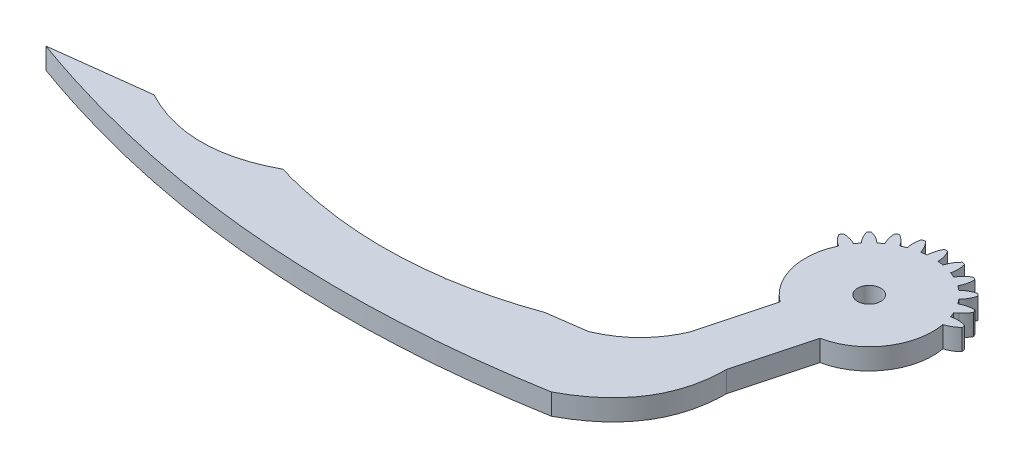
SolidWorks part; units mm, degrees
note: The reader was unsure of these and kept them because the rebuilt part matched: shared geometry of "Sketch6<3>".
ref_plane "Front Plane" through (0, 0, 0) normal (0, 0, 1) x (1, 0, 0)
ref_plane "Top Plane" through (0, 0, 0) normal (0, 1, 0) x (1, 0, 0)
ref_plane "Right Plane" through (0, 0, 0) normal (1, 0, 0) x (0, 0, -1)
sketch "Sketch1" plane through (0, 0, 0) normal (0, 1, 0) x (1, 0, 0)
  line L0 (19.8585, 7.9795) -> (1.4553, 5.5566)
  line L1 (2.4995, -2.3749) -> (20.9027, 0.0479)
  arc A0 (1.4553, 5.5566) -> (2.7124, 7.0406) centre (-1.969, 9.7321) ccw
  arc A1 (2.7124, 7.0406) -> (2.4004, 7.5811) centre (-10.1063, 0) ccw
  arc A2 (2.4004, 7.5811) -> (-0.1918, 6.9236) centre (2.3906, 2.1811) ccw
  arc A3 (-0.1918, 6.9236) -> (-0.8526, 7.7848) centre (-10.1063, 0) ccw
  arc A4 (-0.8526, 7.7848) -> (0.4534, 10.1184) centre (-4.7651, 11.5066) ccw
  arc A5 (0.4534, 10.1184) -> (0.0121, 10.5598) centre (-10.1063, 0) ccw
  arc A6 (0.0121, 10.5598) -> (-2.3216, 9.2538) centre (1.4003, 5.3412) ccw
  arc A7 (-2.3216, 9.2538) -> (-3.1827, 9.9145) centre (-10.1063, 0) ccw
  arc A8 (-3.1827, 9.9145) -> (-2.5252, 12.5067) centre (-7.9252, 12.4969) ccw
  arc A9 (-2.5252, 12.5067) -> (-3.0658, 12.8188) centre (-10.1063, 0) ccw
  arc A10 (-3.0658, 12.8188) -> (-4.9819, 10.9533) centre (-0.3742, 8.1374) ccw
  arc A11 (-4.9819, 10.9533) -> (-5.9847, 11.3687) centre (-10.1063, 0) ccw
  arc A12 (-5.9847, 11.3687) -> (-6.0205, 14.0427) centre (-11.234, 12.6356) ccw
  arc A13 (-6.0205, 14.0427) -> (-6.6234, 14.2042) centre (-10.1063, 0) ccw
  arc A14 (-6.6234, 14.2042) -> (-7.9914, 11.9064) centre (-2.812, 10.379) ccw
  arc A15 (-7.9914, 11.9064) -> (-9.0676, 12.0481) centre (-10.1063, 0) ccw
  arc A16 (-9.0676, 12.0481) -> (-9.7943, 14.6217) centre (-14.4659, 11.9132) ccw
  arc A17 (-9.7943, 14.6217) -> (-10.4184, 14.6217) centre (-10.1063, 0) ccw
  arc A18 (-10.4184, 14.6217) -> (-11.1451, 12.0481) centre (-5.7468, 11.9132) ccw
  arc A19 (-11.1451, 12.0481) -> (-12.2213, 11.9064) centre (-10.1063, 0) ccw
  arc A20 (-12.2213, 11.9064) -> (-13.5893, 14.2042) centre (-17.4007, 10.379) ccw
  arc A21 (-13.5893, 14.2042) -> (-14.1922, 14.0427) centre (-10.1063, 0) ccw
  arc A22 (-14.1922, 14.0427) -> (-14.228, 11.3687) centre (-8.9787, 12.6356) ccw
  arc A23 (-14.228, 11.3687) -> (-15.2308, 10.9533) centre (-10.1063, 0) ccw
  arc A24 (-15.2308, 10.9533) -> (-17.1469, 12.8188) centre (-19.8385, 8.1374) ccw
  arc A25 (-17.1469, 12.8188) -> (-17.6875, 12.5067) centre (-10.1063, 0) ccw
  arc A26 (-17.6875, 12.5067) -> (-17.03, 9.9145) centre (-12.2875, 12.4969) ccw
  arc A27 (-17.03, 9.9145) -> (-17.8911, 9.2538) centre (-10.1063, 0) ccw
  arc A28 (-17.8911, 9.2538) -> (-20.2247, 10.5598) centre (-21.6129, 5.3412) ccw
  arc A29 (-20.2247, 10.5598) -> (-20.6661, 10.1184) centre (-10.1063, 0) ccw
  arc A30 (-20.6661, 10.1184) -> (-19.3601, 7.7848) centre (-15.4476, 11.5066) ccw
  arc A31 (-19.3601, 7.7848) -> (-20.0209, 6.9236) centre (-10.1063, 0) ccw
  arc A32 (-20.0209, 6.9236) -> (-22.613, 7.5811) centre (-22.6033, 2.1811) ccw
  arc A33 (-22.613, 7.5811) -> (-22.9251, 7.0406) centre (-10.1063, 0) ccw
  arc A34 (-22.9251, 7.0406) -> (-21.0596, 5.1244) centre (-18.2437, 9.7321) ccw
  arc A35 (-21.0596, 5.1244) -> (-21.475, 4.1216) centre (-10.1063, 0) ccw
  arc A36 (-21.475, 4.1216) -> (-24.149, 4.0858) centre (-22.742, -1.1276) ccw
  arc A37 (-24.149, 4.0858) -> (-24.3106, 3.4829) centre (-10.1063, 0) ccw
  arc A38 (-24.3106, 3.4829) -> (-22.0127, 2.1149) centre (-20.4853, 7.2944) ccw
  arc A39 (-22.0127, 2.1149) -> (-22.1544, 1.0388) centre (-10.1063, 0) ccw
  arc A40 (-22.1544, 1.0388) -> (-24.728, 0.3121) centre (-22.0196, -4.3596) ccw
  arc A41 (-24.728, 0.3121) -> (-24.728, -0.3121) centre (-10.1063, 0) ccw
  arc A42 (-24.728, -0.3121) -> (-22.1544, -1.0388) centre (-22.0196, 4.3596) ccw
  arc A43 (-22.1544, -1.0388) -> (-22.0127, -2.1149) centre (-10.1063, 0) ccw
  arc A44 (-22.0127, -2.1149) -> (-24.3106, -3.4829) centre (-20.4853, -7.2944) ccw
  arc A45 (-24.3106, -3.4829) -> (-24.149, -4.0858) centre (-10.1063, 0) ccw
  arc A46 (-24.149, -4.0858) -> (-21.475, -4.1216) centre (-22.742, 1.1276) ccw
  arc A47 (-21.475, -4.1216) -> (-21.0596, -5.1244) centre (-10.1063, 0) ccw
  arc A48 (-21.0596, -5.1244) -> (-22.9251, -7.0406) centre (-18.2437, -9.7321) ccw
  arc A49 (-22.9251, -7.0406) -> (-22.613, -7.5811) centre (-10.1063, 0) ccw
  arc A50 (-22.613, -7.5811) -> (-20.0209, -6.9236) centre (-22.6033, -2.1811) ccw
  arc A51 (-20.0209, -6.9236) -> (-19.3601, -7.7848) centre (-10.1063, 0) ccw
  arc A52 (-19.3601, -7.7848) -> (-20.6661, -10.1184) centre (-15.4476, -11.5066) ccw
  arc A53 (-20.6661, -10.1184) -> (-20.2247, -10.5598) centre (-10.1063, 0) ccw
  arc A54 (-20.2247, -10.5598) -> (-17.8911, -9.2538) centre (-21.6129, -5.3412) ccw
  arc A55 (-17.8911, -9.2538) -> (-17.03, -9.9145) centre (-10.1063, 0) ccw
  arc A56 (-17.03, -9.9145) -> (-17.6875, -12.5067) centre (-12.2875, -12.4969) ccw
  arc A57 (-17.6875, -12.5067) -> (-17.1469, -12.8188) centre (-10.1063, 0) ccw
  arc A58 (-17.1469, -12.8188) -> (-15.2308, -10.9533) centre (-19.8385, -8.1374) ccw
  arc A59 (-15.2308, -10.9533) -> (-14.228, -11.3687) centre (-10.1063, 0) ccw
  arc A60 (-14.228, -11.3687) -> (-14.1922, -14.0427) centre (-8.9787, -12.6356) ccw
  arc A61 (-14.1922, -14.0427) -> (-13.5893, -14.2042) centre (-10.1063, 0) ccw
  arc A62 (-13.5893, -14.2042) -> (-12.2213, -11.9064) centre (-17.4007, -10.379) ccw
  arc A63 (-12.2213, -11.9064) -> (-11.1451, -12.0481) centre (-10.1063, 0) ccw
  arc A64 (-11.1451, -12.0481) -> (-10.4184, -14.6217) centre (-5.7468, -11.9132) ccw
  arc A65 (-10.4184, -14.6217) -> (-9.7943, -14.6217) centre (-10.1063, 0) ccw
  arc A66 (-9.7943, -14.6217) -> (-9.0676, -12.0481) centre (-14.4659, -11.9132) ccw
  arc A67 (-9.0676, -12.0481) -> (-7.9914, -11.9064) centre (-10.1063, 0) ccw
  arc A68 (-7.9914, -11.9064) -> (-6.6234, -14.2042) centre (-2.812, -10.379) ccw
  arc A69 (-6.6234, -14.2042) -> (-6.0205, -14.0427) centre (-10.1063, 0) ccw
  arc A70 (-6.0205, -14.0427) -> (-5.9847, -11.3687) centre (-11.234, -12.6356) ccw
  arc A71 (-5.9847, -11.3687) -> (-4.9819, -10.9533) centre (-10.1063, 0) ccw
  arc A72 (-4.9819, -10.9533) -> (-3.0658, -12.8188) centre (-0.3742, -8.1374) ccw
  arc A73 (-3.0658, -12.8188) -> (-2.5252, -12.5067) centre (-10.1063, 0) ccw
  arc A74 (-2.5252, -12.5067) -> (-3.1827, -9.9145) centre (-7.9252, -12.4969) ccw
  arc A75 (-3.1827, -9.9145) -> (-2.3216, -9.2538) centre (-10.1063, 0) ccw
  arc A76 (-2.3216, -9.2538) -> (0.0121, -10.5598) centre (1.4003, -5.3412) ccw
  arc A77 (0.0121, -10.5598) -> (0.4534, -10.1184) centre (-10.1063, 0) ccw
  arc A78 (0.4534, -10.1184) -> (-0.8526, -7.7848) centre (-4.7651, -11.5066) ccw
  arc A79 (-0.8526, -7.7848) -> (-0.1918, -6.9236) centre (-10.1063, 0) ccw
  arc A80 (-0.1918, -6.9236) -> (2.4004, -7.5811) centre (2.3906, -2.1811) ccw
  arc A81 (2.4004, -7.5811) -> (2.7124, -7.0406) centre (-10.1063, 0) ccw
  arc A82 (2.7124, -7.0406) -> (0.847, -5.1244) centre (-1.969, -9.7321) ccw
  arc A83 (0.847, -5.1244) -> (1.2623, -4.1216) centre (-10.1063, 0) ccw
  arc A84 (1.2623, -4.1216) -> (3.9363, -4.0858) centre (2.5293, 1.1276) ccw
  arc A85 (3.9363, -4.0858) -> (4.0979, -3.4829) centre (-10.1063, 0) ccw
  arc A86 (4.0979, -3.4829) -> (2.4995, -2.3749) centre (0.2726, -7.2944) ccw
  arc A87 (20.9027, 0.0479) -> (19.8585, 7.9795) centre (20.3806, 4.0137) ccw
  circle A88 centre (-10.1063, 0) radius 1.5
  circle A89 centre (20.3806, 4.0137) radius 1.5
  dimension "D1" = 3
  dimension "D2" = 3
extrude "Boss-Extrude1" add sketch "Sketch1" along normal blind 4
sketch "Sketch3" plane through (0, 4, 0) normal (0, 1, 0) x (1, 0, 0)
  line L0 (-10.1063, 0) -> (-40.8563, 0) construction
  line L1 (-10.1063, 0) -> (-40.5933, -4.0137)
  line L2 (-10.6284, 3.9658) -> (-41.1154, -0.0479)
  line L3 (-9.5842, -3.9658) -> (-40.0712, -7.9795)
  line L4 (-10.1063, 0) -> (-6.3211, 14.1267) construction
  line L5 (-10.1063, 0) -> (-10.1063, 14.625) construction
  circle A0 centre (-10.1063, 0) radius 1.5
  circle A1 centre (20.3806, 4.0137) radius 1.5 construction
  circle A2 centre (20.3806, 4.0137) radius 1.5
  circle A3 centre (-40.5933, -4.0137) radius 1.75
  circle A4 centre (-40.5933, -4.0137) radius 4
  circle A5 centre (-10.1063, 0) radius 4
  arc A6 (-6.0205, 14.0427) -> (-6.6234, 14.2042) centre (-10.1063, 0) ccw construction
  arc A7 (-9.7943, 14.6217) -> (-10.4184, 14.6217) centre (-10.1063, 0) ccw construction
  dimension "D2" = 3
  dimension "D5" = 3.5
  dimension "D6" = 8
  dimension "D7" = 8
  dimension "D1" = 30.75
  dimension "D4" = 7.5
extrude "Boss-Extrude2" add sketch "Sketch3" against normal blind 4
sketch "Sketch4" plane through (0, 4, 0) normal (0, 1, 0) x (1, 0, 0)
  line L0 (19.8585, 7.9795) -> (1.4553, 5.5566) construction
  line L1 (2.4995, -2.3749) -> (20.9027, 0.0479) construction
  line L2 (19.8585, 7.9795) -> (1.4553, 5.5566)
  line L3 (2.4995, -2.3749) -> (20.9027, 0.0479)
  line L4 (1.4553, 5.5566) -> (0.8694, 5.0762)
  line L5 (-21.6245, -5.5509) -> (-20.8986, -5.4553)
  line L6 (-10.1063, 0) -> (-0.8526, 7.7848) construction
  line L7 (-10.1063, 0) -> (1.8, 2.1149) construction
  line L8 (-22.7122, 2.3749) -> (-41.1154, -0.0479)
  line L9 (-40.0712, -7.9795) -> (-21.668, -5.5566)
  line L10 (2.4995, -2.3749) -> (20.9027, 0.0479)
  line L11 (19.8585, 7.9795) -> (1.4553, 5.5566)
  line L12 (-21.9429, 2.4762) -> (-41.1154, -0.0479)
  line L13 (-40.0712, -7.9795) -> (-21.6245, -5.5509)
  line L14 (2.4995, -2.3749) -> (20.9027, 0.0479)
  line L15 (19.8585, 7.9795) -> (1.4553, 5.5566)
  circle A0 centre (-10.1063, 0) radius 12.0927
  arc A1 (2.4004, 7.5811) -> (-0.1918, 6.9236) centre (2.3906, 2.1811) ccw construction
  arc A2 (2.7124, 7.0406) -> (2.4004, 7.5811) centre (-10.1063, 0) ccw construction
  arc A3 (1.4553, 5.5566) -> (2.7124, 7.0406) centre (-1.969, 9.7321) ccw construction
  arc A4 (20.9027, 0.0479) -> (19.8585, 7.9795) centre (20.3806, 4.0137) ccw construction
  arc A5 (4.0979, -3.4829) -> (2.4995, -2.3749) centre (0.2726, -7.2944) ccw construction
  arc A6 (3.9363, -4.0858) -> (4.0979, -3.4829) centre (-10.1063, 0) ccw construction
  arc A7 (1.2623, -4.1216) -> (3.9363, -4.0858) centre (2.5293, 1.1276) ccw construction
  arc A8 (2.4004, 7.5811) -> (-0.1918, 6.9236) centre (2.3906, 2.1811) ccw
  arc A9 (2.7124, 7.0406) -> (2.4004, 7.5811) centre (-10.1063, 0) ccw
  arc A10 (1.4553, 5.5566) -> (2.7124, 7.0406) centre (-1.969, 9.7321) ccw
  arc A11 (20.9027, 0.0479) -> (19.8585, 7.9795) centre (20.3806, 4.0137) ccw
  arc A12 (4.0979, -3.4829) -> (2.4995, -2.3749) centre (0.2726, -7.2944) ccw
  arc A13 (3.9363, -4.0858) -> (4.0979, -3.4829) centre (-10.1063, 0) ccw
  arc A14 (1.2623, -4.1216) -> (3.9363, -4.0858) centre (2.5293, 1.1276) ccw
  arc A15 (1.8, 2.1149) -> (4.0979, 3.4829) centre (0.2726, 7.2944) ccw
  arc A16 (3.9363, 4.0858) -> (1.2623, 4.1216) centre (2.5293, -1.1276) ccw
  arc A17 (4.0979, 3.4829) -> (3.9363, 4.0858) centre (-10.1063, 0) ccw
  arc A95 (-21.668, -5.5566) -> (-22.9251, -7.0406) centre (-18.2437, -9.7321) ccw
  arc A96 (-41.1154, -0.0479) -> (-40.0712, -7.9795) centre (-40.5933, -4.0137) ccw
  arc A97 (-19.3601, -7.7848) -> (-20.6661, -10.1184) centre (-15.4476, -11.5066) ccw
  arc A98 (-20.6661, -10.1184) -> (-20.2247, -10.5598) centre (-10.1063, 0) ccw
  arc A99 (-20.2247, -10.5598) -> (-17.8911, -9.2538) centre (-21.6129, -5.3412) ccw
  arc A100 (-17.8911, -9.2538) -> (-17.03, -9.9145) centre (-10.1063, 0) ccw
  arc A101 (-17.03, -9.9145) -> (-17.6875, -12.5067) centre (-12.2875, -12.4969) ccw
  arc A102 (-17.6875, -12.5067) -> (-17.1469, -12.8188) centre (-10.1063, 0) ccw
  arc A103 (-17.1469, -12.8188) -> (-15.2308, -10.9533) centre (-19.8385, -8.1374) ccw
  arc A104 (-15.2308, -10.9533) -> (-14.228, -11.3687) centre (-10.1063, 0) ccw
  arc A105 (-14.228, -11.3687) -> (-14.1922, -14.0427) centre (-8.9787, -12.6356) ccw
  arc A106 (-14.1922, -14.0427) -> (-13.5893, -14.2042) centre (-10.1063, 0) ccw
  arc A107 (-13.5893, -14.2042) -> (-12.2213, -11.9064) centre (-17.4007, -10.379) ccw
  arc A108 (-12.2213, -11.9064) -> (-11.1451, -12.0481) centre (-10.1063, 0) ccw
  arc A109 (-11.1451, -12.0481) -> (-10.4184, -14.6217) centre (-5.7468, -11.9132) ccw
  arc A110 (-10.4184, -14.6217) -> (-9.7943, -14.6217) centre (-10.1063, 0) ccw
  arc A111 (-9.7943, -14.6217) -> (-9.0676, -12.0481) centre (-14.4659, -11.9132) ccw
  arc A112 (-9.0676, -12.0481) -> (-7.9914, -11.9064) centre (-10.1063, 0) ccw
  arc A113 (-7.9914, -11.9064) -> (-6.6234, -14.2042) centre (-2.812, -10.379) ccw
  arc A114 (-6.6234, -14.2042) -> (-6.0205, -14.0427) centre (-10.1063, 0) ccw
  arc A115 (-6.0205, -14.0427) -> (-5.9847, -11.3687) centre (-11.234, -12.6356) ccw
  arc A116 (-5.9847, -11.3687) -> (-4.9819, -10.9533) centre (-10.1063, 0) ccw
  arc A117 (-4.9819, -10.9533) -> (-3.0658, -12.8188) centre (-0.3742, -8.1374) ccw
  arc A118 (-3.0658, -12.8188) -> (-2.5252, -12.5067) centre (-10.1063, 0) ccw
  arc A119 (-2.5252, -12.5067) -> (-3.1827, -9.9145) centre (-7.9252, -12.4969) ccw
  arc A120 (-3.1827, -9.9145) -> (-2.3216, -9.2538) centre (-10.1063, 0) ccw
  arc A121 (-2.3216, -9.2538) -> (0.0121, -10.5598) centre (1.4003, -5.3412) ccw
  arc A122 (0.0121, -10.5598) -> (0.4534, -10.1184) centre (-10.1063, 0) ccw
  arc A123 (0.4534, -10.1184) -> (-0.8526, -7.7848) centre (-4.7651, -11.5066) ccw
  arc A124 (-0.8526, -7.7848) -> (-0.1918, -6.9236) centre (-10.1063, 0) ccw
  arc A125 (-0.1918, -6.9236) -> (2.4004, -7.5811) centre (2.3906, -2.1811) ccw
  arc A126 (2.4004, -7.5811) -> (2.7124, -7.0406) centre (-10.1063, 0) ccw
  arc A127 (2.7124, -7.0406) -> (0.847, -5.1244) centre (-1.969, -9.7321) ccw
  arc A128 (0.847, -5.1244) -> (1.2623, -4.1216) centre (-10.1063, 0) ccw
  arc A129 (1.2623, -4.1216) -> (3.9363, -4.0858) centre (2.5293, 1.1276) ccw
  arc A130 (3.9363, -4.0858) -> (4.0979, -3.4829) centre (-10.1063, 0) ccw
  arc A131 (4.0979, -3.4829) -> (2.4995, -2.3749) centre (0.2726, -7.2944) ccw
  arc A132 (20.9027, 0.0479) -> (19.8585, 7.9795) centre (20.3806, 4.0137) ccw
  arc A133 (1.4553, 5.5566) -> (2.7124, 7.0406) centre (-1.969, 9.7321) ccw
  arc A134 (2.7124, 7.0406) -> (2.4004, 7.5811) centre (-10.1063, 0) ccw
  arc A135 (2.4004, 7.5811) -> (-0.1918, 6.9236) centre (2.3906, 2.1811) ccw
  arc A136 (-0.1918, 6.9236) -> (-0.8526, 7.7848) centre (-10.1063, 0) ccw
  arc A137 (-0.8526, 7.7848) -> (0.4534, 10.1184) centre (-4.7651, 11.5066) ccw
  arc A138 (0.4534, 10.1184) -> (0.0121, 10.5598) centre (-10.1063, 0) ccw
  arc A139 (0.0121, 10.5598) -> (-2.3216, 9.2538) centre (1.4003, 5.3412) ccw
  arc A140 (-2.3216, 9.2538) -> (-3.1827, 9.9145) centre (-10.1063, 0) ccw
  arc A141 (-3.1827, 9.9145) -> (-2.5252, 12.5067) centre (-7.9252, 12.4969) ccw
  arc A142 (-2.5252, 12.5067) -> (-3.0658, 12.8188) centre (-10.1063, 0) ccw
  arc A143 (-3.0658, 12.8188) -> (-4.9819, 10.9533) centre (-0.3742, 8.1374) ccw
  arc A144 (-4.9819, 10.9533) -> (-5.9847, 11.3687) centre (-10.1063, 0) ccw
  arc A145 (-5.9847, 11.3687) -> (-6.0205, 14.0427) centre (-11.234, 12.6356) ccw
  arc A146 (-6.0205, 14.0427) -> (-6.6234, 14.2042) centre (-10.1063, 0) ccw
  arc A147 (-6.6234, 14.2042) -> (-7.9914, 11.9064) centre (-2.812, 10.379) ccw
  arc A148 (-7.9914, 11.9064) -> (-9.0676, 12.0481) centre (-10.1063, 0) ccw
  arc A149 (-9.0676, 12.0481) -> (-9.7943, 14.6217) centre (-14.4659, 11.9132) ccw
  arc A150 (-9.7943, 14.6217) -> (-10.4184, 14.6217) centre (-10.1063, 0) ccw
  arc A151 (-10.4184, 14.6217) -> (-11.1451, 12.0481) centre (-5.7468, 11.9132) ccw
  arc A152 (-11.1451, 12.0481) -> (-12.2213, 11.9064) centre (-10.1063, 0) ccw
  arc A153 (-12.2213, 11.9064) -> (-13.5893, 14.2042) centre (-17.4007, 10.379) ccw
  arc A154 (-13.5893, 14.2042) -> (-14.1922, 14.0427) centre (-10.1063, 0) ccw
  arc A155 (-14.1922, 14.0427) -> (-14.228, 11.3687) centre (-8.9787, 12.6356) ccw
  arc A156 (-14.228, 11.3687) -> (-15.2308, 10.9533) centre (-10.1063, 0) ccw
  arc A157 (-15.2308, 10.9533) -> (-17.1469, 12.8188) centre (-19.8385, 8.1374) ccw
  arc A158 (-17.1469, 12.8188) -> (-17.6875, 12.5067) centre (-10.1063, 0) ccw
  arc A159 (-17.6875, 12.5067) -> (-17.03, 9.9145) centre (-12.2875, 12.4969) ccw
  arc A160 (-17.03, 9.9145) -> (-17.8911, 9.2538) centre (-10.1063, 0) ccw
  arc A161 (-17.8911, 9.2538) -> (-20.2247, 10.5598) centre (-21.6129, 5.3412) ccw
  arc A162 (-20.2247, 10.5598) -> (-20.6661, 10.1184) centre (-10.1063, 0) ccw
  arc A163 (-20.6661, 10.1184) -> (-19.3601, 7.7848) centre (-15.4476, 11.5066) ccw
  arc A164 (-19.3601, 7.7848) -> (-20.0209, 6.9236) centre (-10.1063, 0) ccw
  arc A165 (-20.0209, 6.9236) -> (-22.613, 7.5811) centre (-22.6033, 2.1811) ccw
  arc A166 (-22.613, 7.5811) -> (-22.9251, 7.0406) centre (-10.1063, 0) ccw
  arc A167 (-22.9251, 7.0406) -> (-21.0596, 5.1244) centre (-18.2437, 9.7321) ccw
  arc A168 (-21.0596, 5.1244) -> (-21.475, 4.1216) centre (-10.1063, 0) ccw
  arc A169 (-21.475, 4.1216) -> (-24.149, 4.0858) centre (-22.742, -1.1276) ccw
  arc A170 (-24.149, 4.0858) -> (-24.3106, 3.4829) centre (-10.1063, 0) ccw
  arc A171 (-24.3106, 3.4829) -> (-22.7122, 2.3749) centre (-20.4853, 7.2944) ccw
  arc A172 (-21.668, -5.5566) -> (-22.9251, -7.0406) centre (-18.2437, -9.7321) ccw
  arc A175 (-22.613, -7.5811) -> (-20.0209, -6.9236) centre (-22.6033, -2.1811) ccw
  arc A176 (-41.1154, -0.0479) -> (-40.0712, -7.9795) centre (-40.5933, -4.0137) ccw
  arc A177 (-19.3601, -7.7848) -> (-20.6661, -10.1184) centre (-15.4476, -11.5066) ccw
  arc A178 (-20.6661, -10.1184) -> (-20.2247, -10.5598) centre (-10.1063, 0) ccw
  arc A179 (-20.2247, -10.5598) -> (-17.8911, -9.2538) centre (-21.6129, -5.3412) ccw
  arc A180 (-17.8911, -9.2538) -> (-17.03, -9.9145) centre (-10.1063, 0) ccw
  arc A181 (-17.03, -9.9145) -> (-17.6875, -12.5067) centre (-12.2875, -12.4969) ccw
  arc A182 (-17.6875, -12.5067) -> (-17.1469, -12.8188) centre (-10.1063, 0) ccw
  arc A183 (-17.1469, -12.8188) -> (-15.2308, -10.9533) centre (-19.8385, -8.1374) ccw
  arc A184 (-15.2308, -10.9533) -> (-14.228, -11.3687) centre (-10.1063, 0) ccw
  arc A185 (-14.228, -11.3687) -> (-14.1922, -14.0427) centre (-8.9787, -12.6356) ccw
  arc A186 (-14.1922, -14.0427) -> (-13.5893, -14.2042) centre (-10.1063, 0) ccw
  arc A187 (-13.5893, -14.2042) -> (-12.2213, -11.9064) centre (-17.4007, -10.379) ccw
  arc A188 (-12.2213, -11.9064) -> (-11.1451, -12.0481) centre (-10.1063, 0) ccw
  arc A189 (-11.1451, -12.0481) -> (-10.4184, -14.6217) centre (-5.7468, -11.9132) ccw
  arc A190 (-10.4184, -14.6217) -> (-9.7943, -14.6217) centre (-10.1063, 0) ccw
  arc A191 (-9.7943, -14.6217) -> (-9.0676, -12.0481) centre (-14.4659, -11.9132) ccw
  arc A192 (-9.0676, -12.0481) -> (-7.9914, -11.9064) centre (-10.1063, 0) ccw
  arc A193 (-7.9914, -11.9064) -> (-6.6234, -14.2042) centre (-2.812, -10.379) ccw
  arc A194 (-6.6234, -14.2042) -> (-6.0205, -14.0427) centre (-10.1063, 0) ccw
  arc A195 (-6.0205, -14.0427) -> (-5.9847, -11.3687) centre (-11.234, -12.6356) ccw
  arc A196 (-5.9847, -11.3687) -> (-4.9819, -10.9533) centre (-10.1063, 0) ccw
  arc A197 (-4.9819, -10.9533) -> (-3.0658, -12.8188) centre (-0.3742, -8.1374) ccw
  arc A198 (-3.0658, -12.8188) -> (-2.5252, -12.5067) centre (-10.1063, 0) ccw
  arc A199 (-2.5252, -12.5067) -> (-3.1827, -9.9145) centre (-7.9252, -12.4969) ccw
  arc A200 (-3.1827, -9.9145) -> (-2.3216, -9.2538) centre (-10.1063, 0) ccw
  arc A201 (-2.3216, -9.2538) -> (0.0121, -10.5598) centre (1.4003, -5.3412) ccw
  arc A202 (0.0121, -10.5598) -> (0.4534, -10.1184) centre (-10.1063, 0) ccw
  arc A203 (0.4534, -10.1184) -> (-0.8526, -7.7848) centre (-4.7651, -11.5066) ccw
  arc A204 (-0.8526, -7.7848) -> (-0.1918, -6.9236) centre (-10.1063, 0) ccw
  arc A205 (-0.1918, -6.9236) -> (2.4004, -7.5811) centre (2.3906, -2.1811) ccw
  arc A206 (2.4004, -7.5811) -> (2.7124, -7.0406) centre (-10.1063, 0) ccw
  arc A207 (2.7124, -7.0406) -> (0.847, -5.1244) centre (-1.969, -9.7321) ccw
  arc A208 (0.847, -5.1244) -> (1.2623, -4.1216) centre (-10.1063, 0) ccw
  arc A209 (1.2623, -4.1216) -> (3.9363, -4.0858) centre (2.5293, 1.1276) ccw
  arc A210 (3.9363, -4.0858) -> (4.0979, -3.4829) centre (-10.1063, 0) ccw
  arc A211 (4.0979, -3.4829) -> (2.4995, -2.3749) centre (0.2726, -7.2944) ccw
  arc A212 (20.9027, 0.0479) -> (19.8585, 7.9795) centre (20.3806, 4.0137) ccw
  arc A213 (1.4553, 5.5566) -> (2.7124, 7.0406) centre (-1.969, 9.7321) ccw
  arc A214 (2.7124, 7.0406) -> (2.4004, 7.5811) centre (-10.1063, 0) ccw
  arc A215 (2.4004, 7.5811) -> (-0.1918, 6.9236) centre (2.3906, 2.1811) ccw
  arc A216 (-0.1918, 6.9236) -> (-0.8526, 7.7848) centre (-10.1063, 0) ccw
  arc A217 (-0.8526, 7.7848) -> (0.4534, 10.1184) centre (-4.7651, 11.5066) ccw
  arc A218 (0.4534, 10.1184) -> (0.0121, 10.5598) centre (-10.1063, 0) ccw
  arc A219 (0.0121, 10.5598) -> (-2.3216, 9.2538) centre (1.4003, 5.3412) ccw
  arc A220 (-2.3216, 9.2538) -> (-3.1827, 9.9145) centre (-10.1063, 0) ccw
  arc A221 (-3.1827, 9.9145) -> (-2.5252, 12.5067) centre (-7.9252, 12.4969) ccw
  arc A222 (-2.5252, 12.5067) -> (-3.0658, 12.8188) centre (-10.1063, 0) ccw
  arc A223 (-3.0658, 12.8188) -> (-4.9819, 10.9533) centre (-0.3742, 8.1374) ccw
  arc A224 (-4.9819, 10.9533) -> (-5.9847, 11.3687) centre (-10.1063, 0) ccw
  arc A225 (-5.9847, 11.3687) -> (-6.0205, 14.0427) centre (-11.234, 12.6356) ccw
  arc A226 (-6.0205, 14.0427) -> (-6.6234, 14.2042) centre (-10.1063, 0) ccw
  arc A227 (-6.6234, 14.2042) -> (-7.9914, 11.9064) centre (-2.812, 10.379) ccw
  arc A228 (-7.9914, 11.9064) -> (-9.0676, 12.0481) centre (-10.1063, 0) ccw
  arc A229 (-9.0676, 12.0481) -> (-9.7943, 14.6217) centre (-14.4659, 11.9132) ccw
  arc A230 (-9.7943, 14.6217) -> (-10.4184, 14.6217) centre (-10.1063, 0) ccw
  arc A231 (-10.4184, 14.6217) -> (-11.1451, 12.0481) centre (-5.7468, 11.9132) ccw
  arc A232 (-11.1451, 12.0481) -> (-12.2213, 11.9064) centre (-10.1063, 0) ccw
  arc A233 (-12.2213, 11.9064) -> (-13.5893, 14.2042) centre (-17.4007, 10.379) ccw
  arc A234 (-13.5893, 14.2042) -> (-14.1922, 14.0427) centre (-10.1063, 0) ccw
  arc A235 (-14.1922, 14.0427) -> (-14.228, 11.3687) centre (-8.9787, 12.6356) ccw
  arc A236 (-14.228, 11.3687) -> (-15.2308, 10.9533) centre (-10.1063, 0) ccw
  arc A237 (-15.2308, 10.9533) -> (-17.1469, 12.8188) centre (-19.8385, 8.1374) ccw
  arc A238 (-17.1469, 12.8188) -> (-17.6875, 12.5067) centre (-10.1063, 0) ccw
  arc A239 (-17.6875, 12.5067) -> (-17.03, 9.9145) centre (-12.2875, 12.4969) ccw
  arc A240 (-17.03, 9.9145) -> (-17.8911, 9.2538) centre (-10.1063, 0) ccw
  arc A241 (-17.8911, 9.2538) -> (-20.2247, 10.5598) centre (-21.6129, 5.3412) ccw
  arc A242 (-20.2247, 10.5598) -> (-20.6661, 10.1184) centre (-10.1063, 0) ccw
  arc A243 (-20.6661, 10.1184) -> (-19.3601, 7.7848) centre (-15.4476, 11.5066) ccw
  arc A244 (-19.3601, 7.7848) -> (-20.0209, 6.9236) centre (-10.1063, 0) ccw
  arc A245 (-20.0209, 6.9236) -> (-22.613, 7.5811) centre (-22.6033, 2.1811) ccw
  arc A246 (-22.613, 7.5811) -> (-22.9251, 7.0406) centre (-10.1063, 0) ccw
  arc A247 (-22.9251, 7.0406) -> (-21.0596, 5.1244) centre (-18.2437, 9.7321) ccw
  arc A248 (-21.0596, 5.1244) -> (-21.475, 4.1216) centre (-10.1063, 0) ccw
  arc A249 (-21.475, 4.1216) -> (-24.149, 4.0858) centre (-22.742, -1.1276) ccw
  arc A250 (-24.149, 4.0858) -> (-24.3106, 3.4829) centre (-10.1063, 0) ccw
  arc A251 (-24.3106, 3.4829) -> (-22.7122, 2.3749) centre (-20.4853, 7.2944) ccw
  arc A252 (-22.613, -7.5811) -> (-20.0209, -6.9236) centre (-22.6033, -2.1811) ccw
  arc A253 (-20.0209, -6.9236) -> (-19.3601, -7.7848) centre (-10.1063, 0) ccw
  arc A254 (-20.0209, -6.9236) -> (-19.3601, -7.7848) centre (-10.1063, 0) ccw
  arc A255 (-22.9251, -7.0406) -> (-22.613, -7.5811) centre (-10.1063, 0) ccw
  arc A256 (-22.9251, -7.0406) -> (-22.613, -7.5811) centre (-10.1063, 0) ccw
  point P40 (-10.1063, 0)
  dimension "D2" = 24.1855
  dimension "D4" = 30
  dimension "D1" = 0
  dimension "D3" = 2
extrude "Cut-Extrude1" cut sketch "Sketch4" against normal blind 4
sketch "Sketch5" plane through (0, 4, 0) normal (0, 1, 0) x (1, 0, 0)
  circle A0 centre (-10.1063, 0) radius 2.2
  circle A1 centre (-5.6063, 0) radius 1.3
  circle A2 centre (-14.6063, 0) radius 1.3
  circle A3 centre (-10.1063, 0) radius 1.5 construction
  dimension "D1" = 4.4
  dimension "D2" = 2.6
  dimension "D3" = 2.6
  dimension "D4" = 4.5
  dimension "D5" = 9
extrude "Cut-Extrude2" cut sketch "Sketch5" against normal up to next contours A0
sketch "Sketch6" plane through (0, 4, 0) normal (0, 1, 0) x (1, 0, 0)
  line L0 (-10.1063, 0) -> (27.4558, 0) construction
  line L6 (-10.1063, 0) -> (-10.1063, 50.6275) construction
  line L7 (-49.9947, -31.0378) -> (-31.4327, -31.0378)
  line L9 (-31.4327, -31.0378) -> (-30.7345, -31.267)
  line L10 (-110.9546, -35.0378) -> (-129.2447, -37.2757)
  line L11 (-16.653, -6.8971) -> (-20.9868, -23.0712)
  line L12 (-6.9937, -9.4853) -> (-11.3793, -25.8525)
  line L15 (0.8694, 5.0762) -> (1.4553, 5.5566)
  line L16 (-7.7003, -31.4377) -> (-7.0568, -31.0378)
  line L17 (-30.7064, -32.7034) -> (-49.8584, -35.379)
  line L18 (-21.9429, 2.4762) -> (-41.1154, -0.0479)
  line L19 (-40.0712, -7.9795) -> (-20.8986, -5.4553)
  line L20 (0.8694, 5.0762) -> (1.4553, 5.5566)
  line L21 (-23.6599, -5.715) -> (-42.8324, -8.2391)
  line L22 (-41.7882, -16.1707) -> (-22.6156, -13.6466)
  line L23 (-21.9429, 2.4762) -> (-41.1154, -0.0479) construction
  line L24 (-21.9429, 2.4762) -> (-41.1154, -0.0479)
  line L25 (-20.8986, -5.4553) -> (-40.0712, -7.9795) construction
  line L26 (-20.8986, -5.4553) -> (-40.0712, -7.9795)
  arc A46 (-20.9868, -23.0712) -> (-31.1213, -32.7614) centre (-19.2447, -35.0378) ccw
  arc A92 (-4.7074, -33.4387) -> (3.539, -25.9102) centre (-0.5842, -29.6745) cw
  arc A93 (-4.7889, -32.8199) -> (-4.7074, -33.4387) centre (-19.2447, -35.0378) cw
  arc A94 (-7.4353, -32.4354) -> (-4.7889, -32.8199) centre (-6.8644, -37.8051) cw
  arc A95 (-7.7163, -31.3869) -> (-7.4353, -32.4354) centre (-19.2447, -35.0378) cw
  arc A96 (-5.6166, -29.7307) -> (-7.7163, -31.3869) centre (-9.9067, -26.4511) cw
  arc A97 (-5.8555, -29.154) -> (-5.6166, -29.7307) centre (-19.2447, -35.0378) cw
  arc A98 (-8.5113, -29.4676) -> (-5.8555, -29.154) centre (-6.57, -34.5065) cw
  arc A99 (-9.054, -28.5275) -> (-8.5113, -29.4676) centre (-19.2447, -35.0378) cw
  arc A100 (-7.4546, -26.3843) -> (-9.054, -28.5275) centre (-12.4473, -24.3268) cw
  arc A101 (-7.8346, -25.8891) -> (-7.4546, -26.3843) centre (-19.2447, -35.0378) cw
  arc A102 (-10.3187, -26.8793) -> (-7.8346, -25.8891) centre (-7.1394, -31.2442) cw
  arc A103 (-11.0863, -26.1118) -> (-10.3187, -26.8793) centre (-19.2447, -35.0378) cw
  arc A104 (-10.096, -23.6277) -> (-11.0863, -26.1118) centre (-15.4511, -22.9325) cw
  arc A105 (-10.5912, -23.2477) -> (-10.096, -23.6277) centre (-19.2447, -35.0378) cw
  arc A106 (-10.6929, -23.2908) -> (-10.5912, -23.2477) centre (-8.5337, -28.2404) cw
  arc A115 (-20.8438, -20.5005) -> (-20.4536, -21.0814) centre (-25.122, -23.7956) cw
  arc A116 (-21.4627, -20.582) -> (-20.8438, -20.5005) centre (-19.2447, -35.0378) cw
  arc A117 (-21.8472, -23.2284) -> (-21.4627, -20.582) centre (-16.4775, -22.6575) cw
  arc A118 (-22.8956, -23.5094) -> (-21.8472, -23.2284) centre (-19.2447, -35.0378) cw
  arc A119 (-24.5519, -21.4097) -> (-22.8956, -23.5094) centre (-27.8314, -25.6998) cw
  arc A120 (-25.1285, -21.6486) -> (-24.5519, -21.4097) centre (-19.2447, -35.0378) cw
  arc A121 (-24.815, -24.3044) -> (-25.1285, -21.6486) centre (-19.776, -22.3631) cw
  arc A122 (-25.755, -24.8471) -> (-24.815, -24.3044) centre (-19.2447, -35.0378) cw
  arc A123 (-27.8983, -23.2477) -> (-25.755, -24.8471) centre (-29.9557, -28.2404) cw
  arc A124 (-28.3934, -23.6277) -> (-27.8983, -23.2477) centre (-19.2447, -35.0378) cw
  arc A125 (-27.4032, -26.1118) -> (-28.3934, -23.6277) centre (-23.0384, -22.9325) cw
  arc A126 (-28.1707, -26.8793) -> (-27.4032, -26.1118) centre (-19.2447, -35.0378) cw
  arc A127 (-30.6549, -25.8891) -> (-28.1707, -26.8793) centre (-31.3501, -31.2442) cw
  arc A128 (-31.0349, -26.3843) -> (-30.6549, -25.8891) centre (-19.2447, -35.0378) cw
  arc A129 (-29.4355, -28.5275) -> (-31.0349, -26.3843) centre (-26.0422, -24.3268) cw
  arc A130 (-29.9782, -29.4676) -> (-29.4355, -28.5275) centre (-19.2447, -35.0378) cw
  arc A131 (-32.634, -29.154) -> (-29.9782, -29.4676) centre (-31.9195, -34.5065) cw
  arc A132 (-32.8728, -29.7307) -> (-32.634, -29.154) centre (-19.2447, -35.0378) cw
  arc A133 (-31.4327, -31.0378) -> (-32.8728, -29.7307) centre (-28.5828, -26.4511) cw
  arc A134 (-52.9621, -37.7202) -> (-49.9947, -31.0378) centre (-49.9947, -35.0378) cw
  arc A135 (3.539, -25.9102) -> (-24.3078, -46.1789) centre (-16.9719, -26.9941) cw
  arc A136 (-8.1265, -11.9296) -> (-17.7857, -9.3414) centre (-10.1063, 0) ccw
  arc A137 (-24.0523, -46.1339) -> (-11.3793, -25.8525) centre (-19.2447, -35.0378) ccw
  arc A138 (-24.0523, -46.1339) -> (-11.3793, -25.8525) centre (-19.2447, -35.0378) ccw
  arc A139 (-20.9868, -23.0712) -> (-31.1213, -32.7614) centre (-19.2447, -35.0378) ccw
  arc A186 (1.4553, 5.5566) -> (2.7124, 7.0406) centre (-1.969, 9.7321) ccw
  arc A187 (2.7124, 7.0406) -> (2.4004, 7.5811) centre (-10.1063, 0) ccw
  arc A188 (2.4004, 7.5811) -> (-0.1918, 6.9236) centre (2.3906, 2.1811) ccw
  arc A189 (-0.1918, 6.9236) -> (-0.8526, 7.7848) centre (-10.1063, 0) ccw
  arc A190 (-0.8526, 7.7848) -> (0.4534, 10.1184) centre (-4.7651, 11.5066) ccw
  arc A191 (0.4534, 10.1184) -> (0.0121, 10.5598) centre (-10.1063, 0) ccw
  arc A192 (0.0121, 10.5598) -> (-2.3216, 9.2538) centre (1.4003, 5.3412) ccw
  arc A193 (-2.3216, 9.2538) -> (-3.1827, 9.9145) centre (-10.1063, 0) ccw
  arc A194 (-3.1827, 9.9145) -> (-2.5252, 12.5067) centre (-7.9252, 12.4969) ccw
  arc A195 (-2.5252, 12.5067) -> (-3.0658, 12.8188) centre (-10.1063, 0) ccw
  arc A196 (-3.0658, 12.8188) -> (-4.9819, 10.9533) centre (-0.3742, 8.1374) ccw
  arc A197 (-4.9819, 10.9533) -> (-5.9847, 11.3687) centre (-10.1063, 0) ccw
  arc A198 (-5.9847, 11.3687) -> (-6.0205, 14.0427) centre (-11.234, 12.6356) ccw
  arc A199 (-6.0205, 14.0427) -> (-6.6234, 14.2042) centre (-10.1063, 0) ccw
  arc A200 (-6.6234, 14.2042) -> (-7.9914, 11.9064) centre (-2.812, 10.379) ccw
  arc A201 (-7.9914, 11.9064) -> (-9.0676, 12.0481) centre (-10.1063, 0) ccw
  arc A202 (-9.0676, 12.0481) -> (-9.7943, 14.6217) centre (-14.4659, 11.9132) ccw
  arc A203 (-9.7943, 14.6217) -> (-10.4184, 14.6217) centre (-10.1063, 0) ccw
  arc A204 (-10.4184, 14.6217) -> (-11.1451, 12.0481) centre (-5.7468, 11.9132) ccw
  arc A205 (-11.1451, 12.0481) -> (-12.2213, 11.9064) centre (-10.1063, 0) ccw
  arc A206 (-12.2213, 11.9064) -> (-13.5893, 14.2042) centre (-17.4007, 10.379) ccw
  arc A207 (-13.5893, 14.2042) -> (-14.1922, 14.0427) centre (-10.1063, 0) ccw
  arc A208 (-14.1922, 14.0427) -> (-14.228, 11.3687) centre (-8.9787, 12.6356) ccw
  arc A209 (-14.228, 11.3687) -> (-15.2308, 10.9533) centre (-10.1063, 0) ccw
  arc A210 (-15.2308, 10.9533) -> (-17.1469, 12.8188) centre (-19.8385, 8.1374) ccw
  arc A211 (-17.1469, 12.8188) -> (-17.6875, 12.5067) centre (-10.1063, 0) ccw
  arc A212 (-17.6875, 12.5067) -> (-17.03, 9.9145) centre (-12.2875, 12.4969) ccw
  arc A213 (-17.03, 9.9145) -> (-17.8911, 9.2538) centre (-10.1063, 0) ccw
  arc A214 (-17.8911, 9.2538) -> (-20.2247, 10.5598) centre (-21.6129, 5.3412) ccw
  arc A215 (-20.2247, 10.5598) -> (-20.6661, 10.1184) centre (-10.1063, 0) ccw
  arc A216 (-20.6661, 10.1184) -> (-19.3601, 7.7848) centre (-15.4476, 11.5066) ccw
  arc A217 (-19.3601, 7.7848) -> (-20.0209, 6.9236) centre (-10.1063, 0) ccw
  arc A218 (-20.0209, 6.9236) -> (-22.613, 7.5811) centre (-22.6033, 2.1811) ccw
  arc A219 (-22.613, 7.5811) -> (-22.9251, 7.0406) centre (-10.1063, 0) ccw
  arc A220 (-22.9251, 7.0406) -> (-21.0596, 5.1244) centre (-18.2437, 9.7321) ccw
  arc A221 (-21.0596, 5.1244) -> (-21.9429, 2.4762) centre (-10.1063, 0) ccw
  arc A226 (-41.1154, -0.0479) -> (-40.0712, -7.9795) centre (-40.5933, -4.0137) ccw
  arc A227 (-20.8986, -5.4553) -> (1.8, 2.1149) centre (-10.1063, 0) ccw
  arc A228 (-7.0568, -31.0378) -> (-5.6166, -29.7307) centre (-9.9067, -26.4511) ccw
  arc A229 (-5.6166, -29.7307) -> (-5.8555, -29.154) centre (-19.2447, -35.0378) ccw
  arc A230 (-5.8555, -29.154) -> (-8.5113, -29.4676) centre (-6.57, -34.5065) ccw
  arc A231 (-8.5113, -29.4676) -> (-9.054, -28.5275) centre (-19.2447, -35.0378) ccw
  arc A232 (-9.054, -28.5275) -> (-7.4546, -26.3843) centre (-12.4473, -24.3268) ccw
  arc A233 (-7.4546, -26.3843) -> (-7.8346, -25.8891) centre (-19.2447, -35.0378) ccw
  arc A234 (-7.8346, -25.8891) -> (-10.3187, -26.8793) centre (-7.1394, -31.2442) ccw
  arc A235 (-10.3187, -26.8793) -> (-11.0863, -26.1118) centre (-19.2447, -35.0378) ccw
  arc A236 (-11.0863, -26.1118) -> (-10.096, -23.6277) centre (-15.4511, -22.9325) ccw
  arc A237 (-10.096, -23.6277) -> (-10.5912, -23.2477) centre (-19.2447, -35.0378) ccw
  arc A238 (-10.5912, -23.2477) -> (-10.6929, -23.2908) centre (-8.5337, -28.2404) ccw
  arc A239 (1.8, 2.1149) -> (4.0979, 3.4829) centre (0.2726, 7.2944) ccw
  arc A240 (4.0979, 3.4829) -> (3.9363, 4.0858) centre (-10.1063, 0) ccw
  arc A241 (3.9363, 4.0858) -> (1.2623, 4.1216) centre (2.5293, -1.1276) ccw
  arc A242 (1.2623, 4.1216) -> (0.8694, 5.0762) centre (-10.1063, 0) ccw
  arc A243 (1.4553, 5.5566) -> (2.7124, 7.0406) centre (-1.969, 9.7321) ccw
  arc A244 (2.7124, 7.0406) -> (2.4004, 7.5811) centre (-10.1063, 0) ccw
  arc A245 (2.4004, 7.5811) -> (-0.1918, 6.9236) centre (2.3906, 2.1811) ccw
  arc A246 (-0.1918, 6.9236) -> (-0.8526, 7.7848) centre (-10.1063, 0) ccw
  arc A247 (-0.8526, 7.7848) -> (0.4534, 10.1184) centre (-4.7651, 11.5066) ccw
  arc A248 (-20.4536, -21.0814) -> (-20.8438, -20.5005) centre (-25.122, -23.7956) ccw
  arc A249 (-20.8438, -20.5005) -> (-21.4627, -20.582) centre (-19.2447, -35.0378) ccw
  arc A250 (-21.4627, -20.582) -> (-21.8472, -23.2284) centre (-16.4775, -22.6575) ccw
  arc A251 (-21.8472, -23.2284) -> (-22.8956, -23.5094) centre (-19.2447, -35.0378) ccw
  arc A252 (-22.8956, -23.5094) -> (-24.5519, -21.4097) centre (-27.8314, -25.6998) ccw
  arc A253 (-24.5519, -21.4097) -> (-25.1285, -21.6486) centre (-19.2447, -35.0378) ccw
  arc A254 (-25.1285, -21.6486) -> (-24.815, -24.3044) centre (-19.776, -22.3631) ccw
  arc A255 (-24.815, -24.3044) -> (-25.755, -24.8471) centre (-19.2447, -35.0378) ccw
  arc A256 (-25.755, -24.8471) -> (-27.8983, -23.2477) centre (-29.9557, -28.2404) ccw
  arc A257 (-27.8983, -23.2477) -> (-28.3934, -23.6277) centre (-19.2447, -35.0378) ccw
  arc A258 (-28.3934, -23.6277) -> (-27.4032, -26.1118) centre (-23.0384, -22.9325) ccw
  arc A259 (-27.4032, -26.1118) -> (-28.1707, -26.8793) centre (-19.2447, -35.0378) ccw
  arc A260 (-28.1707, -26.8793) -> (-30.6549, -25.8891) centre (-31.3501, -31.2442) ccw
  arc A261 (-30.6549, -25.8891) -> (-31.0349, -26.3843) centre (-19.2447, -35.0378) ccw
  arc A262 (-31.0349, -26.3843) -> (-29.4355, -28.5275) centre (-26.0422, -24.3268) ccw
  arc A263 (-29.4355, -28.5275) -> (-29.9782, -29.4676) centre (-19.2447, -35.0378) ccw
  arc A264 (-29.9782, -29.4676) -> (-32.634, -29.154) centre (-31.9195, -34.5065) ccw
  arc A265 (-32.634, -29.154) -> (-32.8728, -29.7307) centre (-19.2447, -35.0378) ccw
  arc A266 (-32.8728, -29.7307) -> (-30.7732, -31.3869) centre (-28.5828, -26.4511) ccw
  arc A267 (-30.7732, -31.3869) -> (-30.7064, -32.7034) centre (-18.6805, -31.4331) ccw
  arc A268 (-49.8584, -35.379) -> (-52.9621, -37.7202) centre (-49.3049, -39.3405) ccw
  arc A269 (-20.5159, -47.0636) -> (3.539, -25.9102) centre (-8.4884, -36.4869) ccw
  arc A270 (3.539, -25.9102) -> (-4.7074, -33.4387) centre (-0.5842, -29.6745) ccw
  arc A271 (-4.7074, -33.4387) -> (-4.7889, -32.8199) centre (-19.2447, -35.0378) ccw
  arc A272 (-4.7889, -32.8199) -> (-7.4353, -32.4354) centre (-6.8644, -37.8051) ccw
  arc A273 (-7.4353, -32.4354) -> (-7.7003, -31.4377) centre (-19.2447, -35.0378) ccw
  arc A274 (0.4534, 10.1184) -> (0.0121, 10.5598) centre (-10.1063, 0) ccw
  arc A275 (0.0121, 10.5598) -> (-2.3216, 9.2538) centre (1.4003, 5.3412) ccw
  arc A276 (-2.3216, 9.2538) -> (-3.1827, 9.9145) centre (-10.1063, 0) ccw
  arc A277 (-3.1827, 9.9145) -> (-2.5252, 12.5067) centre (-7.9252, 12.4969) ccw
  arc A278 (-2.5252, 12.5067) -> (-3.0658, 12.8188) centre (-10.1063, 0) ccw
  arc A279 (-3.0658, 12.8188) -> (-4.9819, 10.9533) centre (-0.3742, 8.1374) ccw
  arc A280 (-4.9819, 10.9533) -> (-5.9847, 11.3687) centre (-10.1063, 0) ccw
  arc A281 (-5.9847, 11.3687) -> (-6.0205, 14.0427) centre (-11.234, 12.6356) ccw
  arc A282 (-6.0205, 14.0427) -> (-6.6234, 14.2042) centre (-10.1063, 0) ccw
  arc A283 (-6.6234, 14.2042) -> (-7.9914, 11.9064) centre (-2.812, 10.379) ccw
  arc A284 (-7.9914, 11.9064) -> (-9.0676, 12.0481) centre (-10.1063, 0) ccw
  arc A285 (-9.0676, 12.0481) -> (-9.7943, 14.6217) centre (-14.4659, 11.9132) ccw
  arc A286 (-9.7943, 14.6217) -> (-10.4184, 14.6217) centre (-10.1063, 0) ccw
  arc A287 (-10.4184, 14.6217) -> (-11.1451, 12.0481) centre (-5.7468, 11.9132) ccw
  arc A288 (-11.1451, 12.0481) -> (-12.2213, 11.9064) centre (-10.1063, 0) ccw
  arc A289 (-12.2213, 11.9064) -> (-13.5893, 14.2042) centre (-17.4007, 10.379) ccw
  arc A290 (-13.5893, 14.2042) -> (-14.1922, 14.0427) centre (-10.1063, 0) ccw
  arc A291 (-14.1922, 14.0427) -> (-14.228, 11.3687) centre (-8.9787, 12.6356) ccw
  arc A292 (-14.228, 11.3687) -> (-15.2308, 10.9533) centre (-10.1063, 0) ccw
  arc A293 (-15.2308, 10.9533) -> (-17.1469, 12.8188) centre (-19.8385, 8.1374) ccw
  arc A294 (-17.1469, 12.8188) -> (-17.6875, 12.5067) centre (-10.1063, 0) ccw
  arc A295 (-17.6875, 12.5067) -> (-17.03, 9.9145) centre (-12.2875, 12.4969) ccw
  arc A296 (-17.03, 9.9145) -> (-17.8911, 9.2538) centre (-10.1063, 0) ccw
  arc A297 (-17.8911, 9.2538) -> (-20.2247, 10.5598) centre (-21.6129, 5.3412) ccw
  arc A298 (-20.2247, 10.5598) -> (-20.6661, 10.1184) centre (-10.1063, 0) ccw
  arc A299 (-20.6661, 10.1184) -> (-19.3601, 7.7848) centre (-15.4476, 11.5066) ccw
  arc A300 (-19.3601, 7.7848) -> (-20.0209, 6.9236) centre (-10.1063, 0) ccw
  arc A301 (-20.0209, 6.9236) -> (-22.613, 7.5811) centre (-22.6033, 2.1811) ccw
  arc A302 (-22.613, 7.5811) -> (-22.9251, 7.0406) centre (-10.1063, 0) ccw
  arc A303 (-22.9251, 7.0406) -> (-21.0596, 5.1244) centre (-18.2437, 9.7321) ccw
  arc A304 (-21.0596, 5.1244) -> (-21.9429, 2.4762) centre (-10.1063, 0) ccw
  arc A309 (-42.8324, -8.2391) -> (-41.7882, -16.1707) centre (-42.3103, -12.2049) ccw
  arc A310 (-20.8986, -5.4553) -> (1.8, 2.1149) centre (-10.1063, 0) ccw
  arc A311 (1.8, 2.1149) -> (4.0979, 3.4829) centre (0.2726, 7.2944) ccw
  arc A312 (4.0979, 3.4829) -> (3.9363, 4.0858) centre (-10.1063, 0) ccw
  arc A313 (3.9363, 4.0858) -> (1.2623, 4.1216) centre (2.5293, -1.1276) ccw
  arc A314 (1.2623, 4.1216) -> (0.8694, 5.0762) centre (-10.1063, 0) ccw
  arc A315 (-41.1154, -0.0479) -> (-40.0712, -7.9795) centre (-40.5933, -4.0137) ccw construction
  circle A316 centre (-40.5933, -4.0137) radius 1.75
  circle A317 centre (-40.5933, -4.0137) radius 1.75
  arc A318 (-41.1154, -0.0479) -> (-40.0712, -7.9795) centre (-40.5933, -4.0137) ccw
  spline S0 degree 2 poles (-30.7064, -32.7034) (-23.8892, -29.8109) (-20.9868, -23.0712) knots 0 0 0 1 1 1
  spline S1 degree 2 poles (-24.3078, -46.1789) (-11.3259, -39.2979) (-11.3793, -25.8525) knots 0 0 0 1 1 1
  spline S3 degree 2 poles (-24.0523, -46.1339) (-78.4311, -55.7367) (-129.2447, -37.2757) knots 0 0 0 1 1 1
  spline S4 degree 2 poles (-86.4738, -35.0378) (-98.6793, -41.5996) (-110.9546, -35.0378) knots 0 0 0 1 1 1
  spline S5 degree 2 poles (-31.4327, -31.0378) (-58.3731, -43.3272) (-86.4738, -35.0378) knots 0 0 0 1 1 1
  dimension "D1" = 0
  dimension "D2" = 27.8535
  dimension "D3" = 0
extrude "Boss-Extrude3" add sketch "Sketch6" against normal up to surface (4 mm away) contours L17 S5 A268 A134 S4 L10 S3 S1 L12 A310 L11 S0 up to face at (-10.1063, 0, 2.2)
extrude "Cut-Extrude3" cut sketch "Sketch6<3>" against normal blind 10 contours S5 L17 A268 | L21 A309 L22 A136
sketch "Sketch6<3>" plane through (0, 4, 0) normal (0, 1, 0) x (1, 0, 0) same geometry as "Sketch6"
